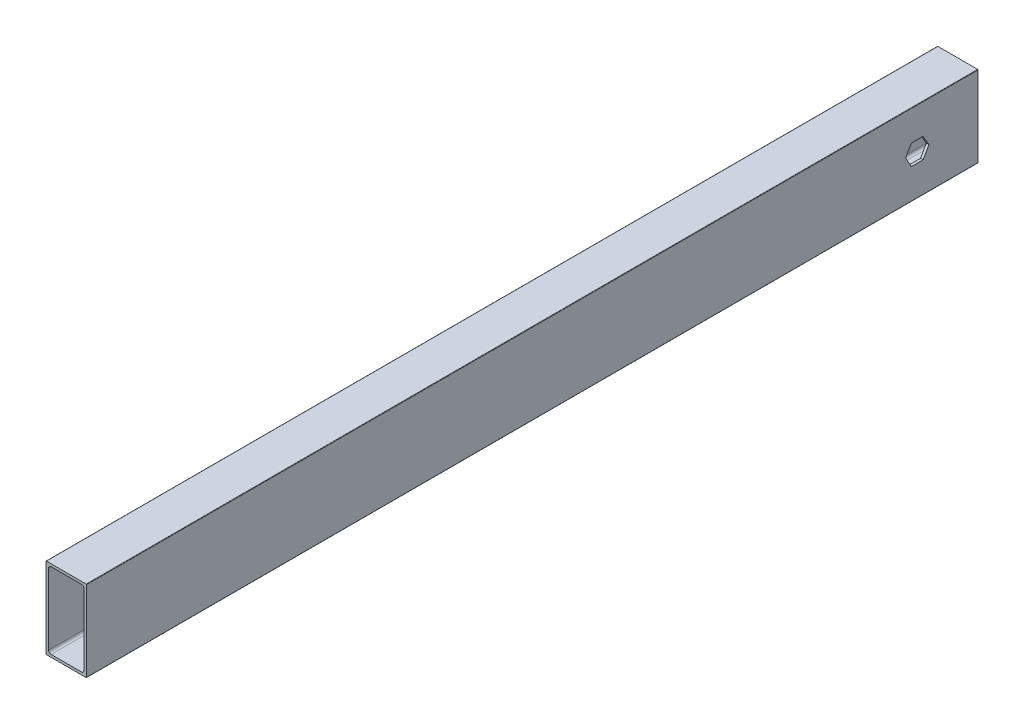
SolidWorks part; units mm, degrees
ref_plane "Front Plane" through (0, 0, 0) normal (0, 0, 1) x (1, 0, 0)
ref_plane "Top Plane" through (0, 0, 0) normal (0, 1, 0) x (1, 0, 0)
ref_plane "Right Plane" through (0, 0, 0) normal (1, 0, 0) x (0, 0, -1)
ref_plane "Plane1" through (0, 0, 0) normal (0, 0, -1) x (-1, 0, 0)
sketch "Sketch1" plane through (0, 0, 0) normal (0, 0, -1) x (-1, 0, 0)
  line L0 (-11.1125, -22.225) -> (-11.1125, 22.225)
  line L1 (-9.525, 23.8125) -> (9.525, 23.8125)
  line L2 (11.1125, 22.225) -> (11.1125, -22.225)
  line L3 (9.525, -23.8125) -> (-9.525, -23.8125)
  line L4 (-12.7, 25.146) -> (-12.7, -25.146)
  line L5 (-12.446, -25.4) -> (12.446, -25.4)
  line L6 (12.7, -25.146) -> (12.7, 25.146)
  line L7 (12.446, 25.4) -> (-12.446, 25.4)
  arc A0 (-11.1125, 22.225) -> (-9.525, 23.8125) centre (-9.525, 22.225) cw
  arc A1 (9.525, 23.8125) -> (11.1125, 22.225) centre (9.525, 22.225) cw
  arc A2 (11.1125, -22.225) -> (9.525, -23.8125) centre (9.525, -22.225) cw
  arc A3 (-9.525, -23.8125) -> (-11.1125, -22.225) centre (-9.525, -22.225) cw
  arc A4 (-12.7, -25.146) -> (-12.446, -25.4) centre (-12.446, -25.146) ccw
  arc A5 (12.446, -25.4) -> (12.7, -25.146) centre (12.446, -25.146) ccw
  arc A6 (12.7, 25.146) -> (12.446, 25.4) centre (12.446, 25.146) ccw
  arc A7 (-12.446, 25.4) -> (-12.7, 25.146) centre (-12.446, 25.146) ccw
extrude "Boss-Extrude1" add sketch "Sketch1" against normal blind 558.8
sketch "Sketch2" plane through (-12.7, 0, 0) normal (-1, 0, 0) x (0, 0, 1)
  line L0 (0, 0) -> (38.1, 0) construction
  line L2 (45.4323, 0) -> (41.7662, 6.35)
  line L3 (41.7662, 6.35) -> (34.4338, 6.35)
  line L4 (34.4338, 6.35) -> (30.7677, 0)
  line L5 (30.7677, 0) -> (34.4338, -6.35)
  line L6 (34.4338, -6.35) -> (41.7662, -6.35)
  line L7 (41.7662, -6.35) -> (45.4323, 0)
  circle A0 centre (38.1, 0) radius 6.35 construction
  dimension "D1" = 12.7
  dimension "D2" = 38.1
extrude "Cut-Extrude1" cut sketch "Sketch2" against normal blind 25.4
